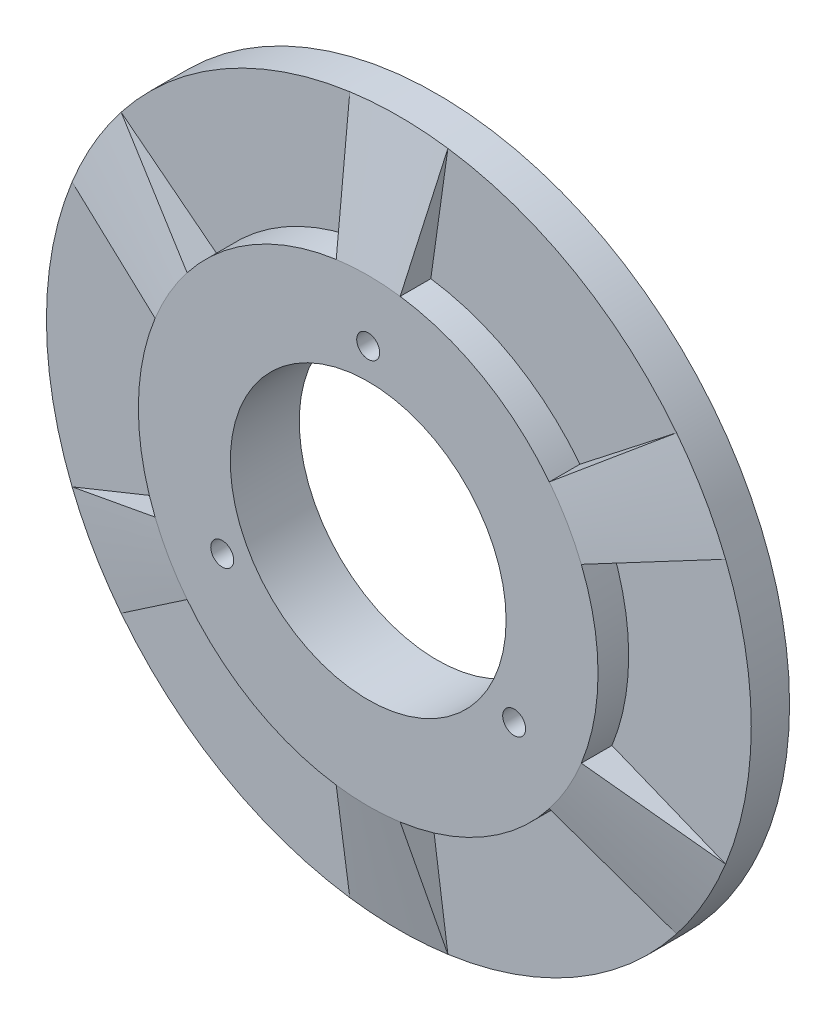
SolidWorks part; units mm, degrees
ref_plane "Front Plane" through (0, 0, 0) normal (0, 0, 1) x (1, 0, 0)
ref_plane "Top Plane" through (0, 0, 0) normal (0, 1, 0) x (1, 0, 0)
ref_plane "Right Plane" through (0, 0, 0) normal (1, 0, 0) x (0, 0, -1)
sketch "Sketch2" plane through (0, 0, 0) normal (0, 0, 1) x (1, 0, 0)
  circle A0 centre (0, 0) radius 46
  circle A2 centre (0, 0) radius 18
  point P13 (0, 0)
  dimension "D1" = 36
  dimension "D2" = 92
extrude "Boss-Extrude2" add sketch "Sketch2" along normal blind 5
sketch "Sketch4" plane through (0, 0, 5) normal (0, 0, 1) x (1, 0, 0)
  circle A0 centre (0, 0) radius 30
  circle A1 centre (0, 0) radius 18
  dimension "D1" = 60
extrude "Boss-Extrude3" add sketch "Sketch4" along normal blind 4
sketch "Sketch5" plane through (0, 0, 0) normal (0, 0, -1) x (-1, 0, 0)
  circle A0 centre (0, 0) radius 22 construction
  circle A1 centre (0, 22) radius 1.5
  circle A2 centre (19.0526, -11) radius 1.5
  circle A3 centre (-19.0526, -11) radius 1.5
  point P11 (0, 0)
  dimension "D1" = 44
  dimension "D2" = 3
  dimension "D3" = 3
extrude "Cut-Extrude1" cut sketch "Sketch5" against normal through all both and the other way through all
sketch "Sketch6" plane through (0, 0, 0) normal (1, 0, 0) x (0, 0, -1)
  line L0 (-5, 30) -> (-9, 30)
  line L1 (-9, 30) -> (-5, 46)
  line L2 (-5, 46) -> (-5, 30)
  line L3 (0, 0) -> (32.6688, 0) construction
revolve "Revolve1" add sketch "Sketch6" angle 16 mid plane about L3
pattern_circular "CirPattern1" count 6 over 360 about axis through (0, 0, 9) along (0, 0, 1) of "Revolve1"
